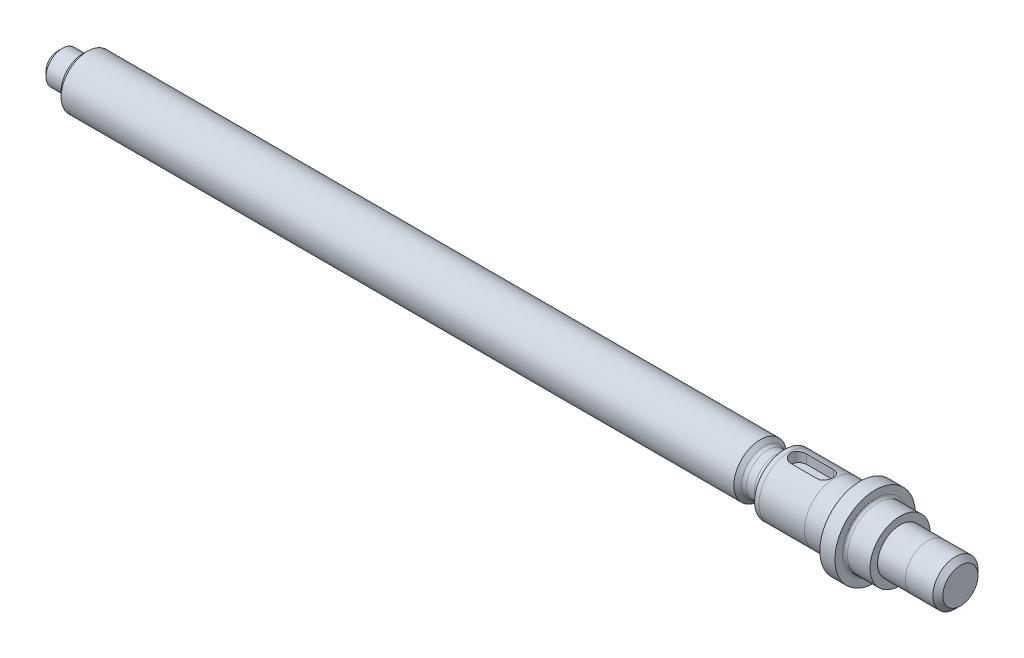
SolidWorks part; units mm, degrees
ref_plane "Спереди" through (0, 0, 0) normal (0, 0, 1) x (1, 0, 0)
ref_plane "Сверху" through (0, 0, 0) normal (0, 1, 0) x (1, 0, 0)
ref_plane "Справа" through (0, 0, 0) normal (1, 0, 0) x (0, 0, -1)
sketch "Эскиз1" plane through (0, 0, 0) normal (0, 1, 0) x (1, 0, 0)
  line L0 (55.7564, -2.4973) -> (55.7564, -6.9973)
  line L1 (55.7564, -6.9973) -> (43.7564, -6.9973)
  line L2 (43.7564, -6.9973) -> (43.7564, -8.4973)
  line L3 (43.7564, -8.4973) -> (38.7564, -8.4973)
  line L4 (38.7564, -8.4973) -> (38.7564, -10.4973)
  line L5 (38.7564, -10.4973) -> (35.7564, -10.4973)
  line L6 (35.7564, -10.4973) -> (35.7564, -8.4973)
  line L7 (35.7564, -8.4973) -> (20.7564, -8.4973)
  line L8 (18.9564, -6.6973) -> (16.9564, -6.6973)
  line L9 (16.9564, -6.6973) -> (15.8958, -7.7579)
  line L10 (15.8958, -7.7579) -> (-119.0894, -7.7579)
  line L11 (-119.0894, -7.7579) -> (-119.0894, -5.7579)
  line L12 (-119.0894, -5.7579) -> (-124.0894, -5.7579)
  line L13 (-124.0894, -5.7579) -> (-124.0894, -2.4973)
  line L14 (-124.0894, -2.1474) -> (-124.0894, -2.4973) construction
  line L15 (-124.0894, -2.4973) -> (55.7564, -2.4973) construction
  line L16 (55.7564, -2.4973) -> (-124.0894, -2.4973)
  arc A0 (20.7564, -8.4973) -> (18.9564, -6.6973) centre (18.9564, -8.4973) ccw
  dimension "D1" = 4.5
  dimension "D2" = 3.2607
revolve "Повернуть1" add sketch "Эскиз1" angle 360 about L16
fillet "Скругление1" radius 0.5 1 edges at (35.7564, 0, -3.5027) type face fillet first side face at (35.7564, 0, -3.5027) second side face at (35.7564, 0, -5.5027)
fillet "Скругление2" radius 0.5 1 edges at (38.7564, 0, -3.5027) type face fillet first side face at (38.7564, 0, -3.5027) second side face at (43.7564, 0, -3.5027)
fillet "Скругление3" radius 1 1 edges at (16.9564, 0, -1.7027) type face fillet first side face at (16.9564, 0, -1.7027) second side face at (18.9564, 0, -1.7027)
fillet "Скругление4" radius 0.5 1 edges at (-119.0894, 0, -0.7634) type face fillet first side face at (-119.0894, 0, -2.7634) second side face at (-119.0894, 0, -0.7634)
chamfer "Фаска1" distance 1 angle 45 2 edges at (55.7564, 0, -2.0027) (-119.0894, 0, -2.7634)
chamfer "Фаска2" distance 1 angle 45 1 edges at (-124.0894, 0, -0.7634)
ref_plane "Плоскость1" through (0, 10, 0) normal (0, 1, 0) x (1, 0, 0)
sketch "Эскиз2" plane through (0, 10, 0) normal (0, 1, 0) x (1, 0, 0)
  line L0 (23.5509, -2.4973) -> (28.8684, -2.4973) construction
  line L1 (23.5509, -0.9029) -> (28.8684, -0.9029)
  line L2 (23.5509, -4.0917) -> (28.8684, -4.0917)
  arc A0 (23.5509, -0.9029) -> (23.5509, -4.0917) centre (23.5509, -2.4973) ccw
  arc A1 (28.8684, -4.0917) -> (28.8684, -0.9029) centre (28.8684, -2.4973) ccw
  point P2 (26.2096, -2.4973)
  point P7 (0, 0)
  point P8 (0, 0)
  point P9 (0, 0)
  point P10 (0, 0)
  point P11 (0, 0)
  point P14 (0, 0)
  point P15 (0, 0)
  point P16 (0, 0)
  point P17 (0, 0)
  point P18 (23.5509, -2.5385)
  point P19 (28.8684, -2.4973)
extrude "Вырез-Вытянуть1" cut sketch "Эскиз2" against normal blind 6
sketch "Эскиз3" plane through (0, 10, 0) normal (0, 1, 0) x (1, 0, 0)
  line L0 (30.681, -10.4132) -> (30.681, 4.2474)
  line L1 (21.6418, -9.6937) -> (21.6418, 6.361)
  point P2 (21.6418, -9.6937)
  point P3 (30.681, -10.4132)
split line "Разделяющая линия4"
sketch "Эскиз4" plane through (0, 10, 0) normal (0, 1, 0) x (1, 0, 0)
  line L0 (49.2564, 2.0027) -> (49.2564, -6.9973)
  line L1 (54.7564, 2.0027) -> (43.7564, 2.0027) construction
  line L2 (43.7564, -6.9973) -> (54.7564, -6.9973) construction
split line "Разделяющая линия5"
